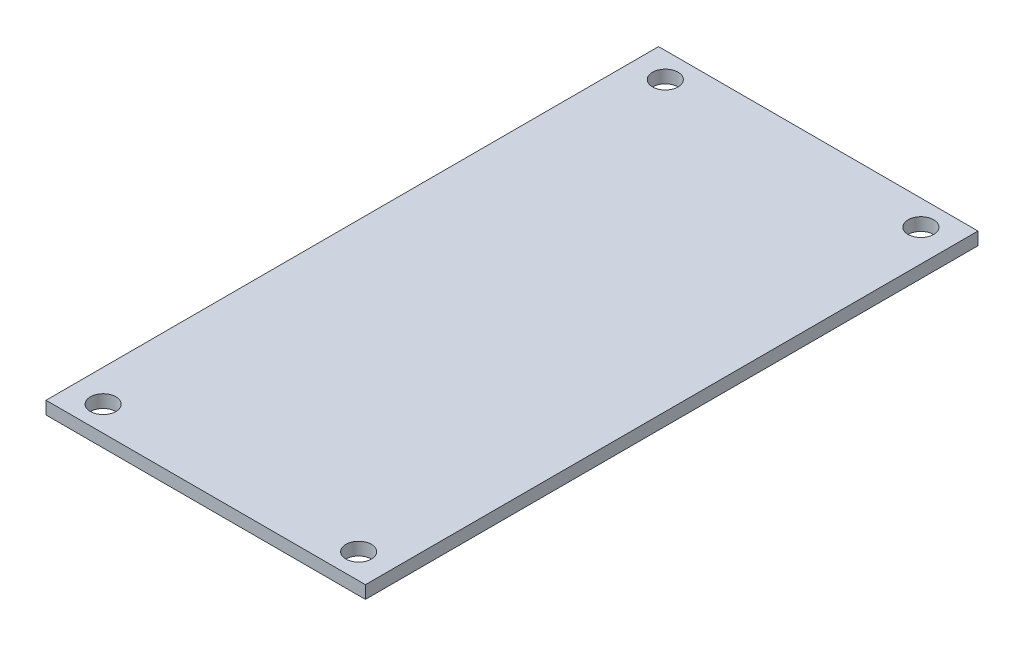
SolidWorks part; units mm, degrees
ref_plane "Front Plane" through (0, 0, 0) normal (0, 0, 1) x (1, 0, 0)
ref_plane "Top Plane" through (0, 0, 0) normal (0, 1, 0) x (1, 0, 0)
ref_plane "Right Plane" through (0, 0, 0) normal (1, 0, 0) x (0, 0, -1)
sketch "Sketch1" plane through (0, 0, 0) normal (0, 1, 0) x (1, 0, 0)
  line L1 (0, 0) -> (125, 0)
  line L2 (0, 0) -> (0, -239.7125)
  line L3 (0, -239.7125) -> (125, -239.7125)
  line L4 (125, 0) -> (125, -239.7125)
  dimension "D1" = 125
  dimension "D2" = 239.7125
extrude "Boss-Extrude1" add sketch "Sketch1" along normal blind 5
sketch "Sketch2" plane through (0, 0, 0) normal (0, -1, 0) x (1, 0, 0)
  line L2 (0, 119.8563) -> (125, 119.8563) construction
  line L5 (0, 0) -> (0, 239.7125) construction
  line L6 (125, 239.7125) -> (125, 0) construction
  line L7 (62.5, 0) -> (62.5, 239.7125) construction
  line L8 (125, 0) -> (0, 0) construction
  line L9 (0, 239.7125) -> (125, 239.7125) construction
  circle A0 centre (12.5, 229.8562) radius 5
  circle A1 centre (112.5, 229.8562) radius 5
  circle A2 centre (12.5, 9.8562) radius 5
  circle A3 centre (112.5, 9.8562) radius 5
  point P0 (12.5, 229.8562)
  point P1 (112.5, 229.8562)
  point P6 (12.5, 9.8562)
  point P7 (112.5, 9.8562)
  point P24 (0, 0)
  point P25 (0, 0)
  point P26 (0, 0)
  point P27 (0, 0)
  dimension "D9" = 10
  dimension "D1" = 100
  dimension "D2" = 110
  dimension "D3" = 50
  dimension "D4" = 220
extrude "Cut-Extrude1" cut sketch "Sketch2" against normal up to next
sketch "Sketch3" plane through (0, 0, 0) normal (0, -1, 0) x (1, 0, 0)
  line L0 (0, 119.8563) -> (125, 119.8563) construction
  line L2 (125, 239.7125) -> (125, 0) construction
  line L3 (0, 0) -> (0, 239.7125) construction
  line L4 (62.5, 239.7125) -> (62.5, 0) construction
  line L6 (125, 0) -> (0, 0) construction
  line L7 (0, 239.7125) -> (125, 239.7125) construction
  point P0 (62.5, 119.8563)
  point P5 (62.5, 119.8563)
  point P12 (62.5, 119.8563)
  point P17 (20.7776, 318.2217)
ref_axis "Axis1" through (112.5, 5, 229.8562) along (0, -1, 0)
